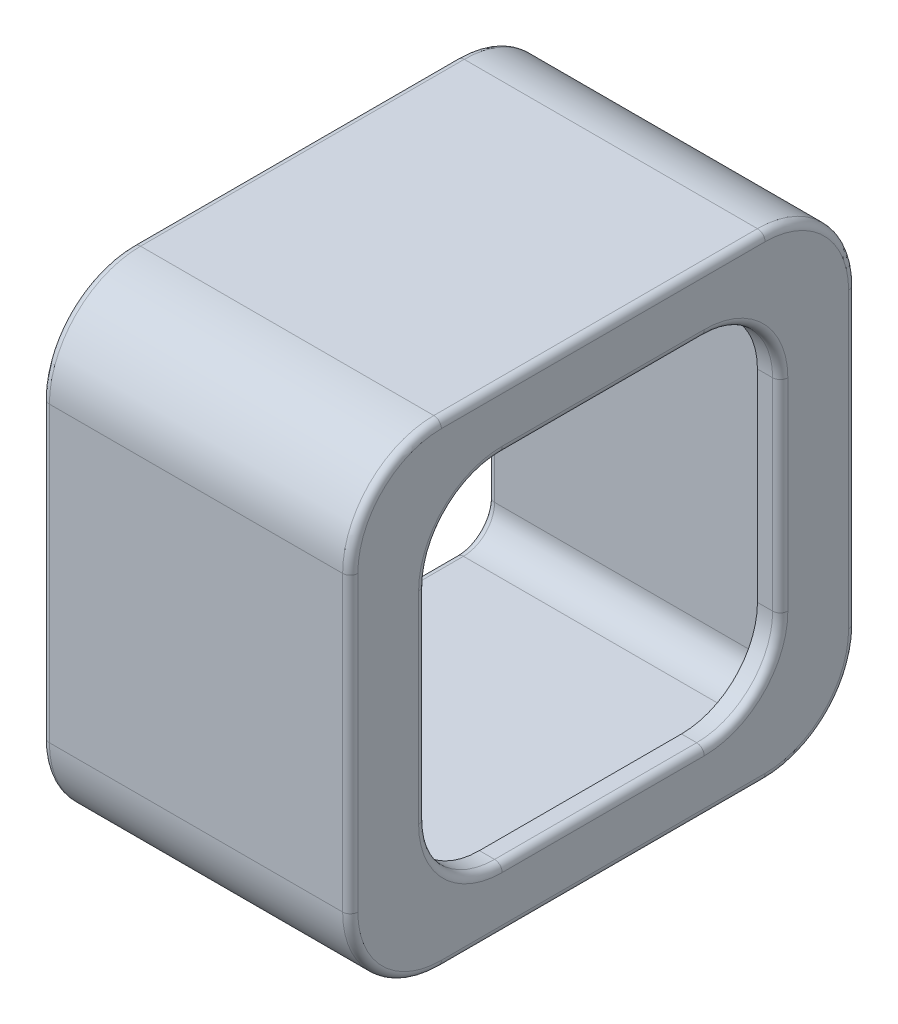
SolidWorks part; units mm, degrees
note: The reader was unsure of these and kept them because the rebuilt part matched: shared geometry of "Sketch1<4>".
ref_plane "Front Plane" through (0, 0, 0) normal (0, 0, 1) x (1, 0, 0)
ref_plane "Top Plane" through (0, 0, 0) normal (0, 1, 0) x (1, 0, 0)
ref_plane "Right Plane" through (0, 0, 0) normal (1, 0, 0) x (0, 0, -1)
ref_plane "Plane1" through (72.6, 0, 0) normal (1, 0, 0) x (0, 0, -1)
sketch "Sketch1" plane through (72.6, 0, 0) normal (1, 0, 0) x (0, 0, -1)
  line L0 (-21.65, 18.55) -> (-8.35, 18.55)
  line L1 (-3.35, 13.55) -> (-3.35, 0.25)
  line L2 (-21.65, -4.75) -> (-8.35, -4.75)
  line L3 (-26.65, 13.55) -> (-26.65, 0.25)
  line L24 (-2.4, 17.5) -> (-2.4, -3.7) construction
  line L25 (-25.6, -5.7) -> (-4.4, -5.7) construction
  line L26 (-27.6, 17.5) -> (-27.6, -3.7) construction
  line L27 (-25.6, 19.5) -> (-4.4, 19.5) construction
  line L28 (-2.4, 17.5) -> (-2.4, -3.7) construction
  line L29 (-25.6, -5.7) -> (-4.4, -5.7) construction
  line L30 (-27.6, 17.5) -> (-27.6, -3.7) construction
  line L31 (-25.6, 19.5) -> (-4.4, 19.5) construction
  line L32 (-25.6, 19.55) -> (-4.4, 19.55)
  line L33 (-2.35, 17.5) -> (-2.35, -3.7)
  line L34 (-25.6, -5.75) -> (-4.4, -5.75)
  line L35 (-27.65, 17.5) -> (-27.65, -3.7)
  line L36 (-25.65, 22.55) -> (-4.35, 22.55)
  line L37 (1.65, 16.55) -> (1.65, -2.75)
  line L38 (-25.65, -8.75) -> (-4.35, -8.75)
  line L39 (-31.65, 16.55) -> (-31.65, -2.75)
  line L40 (-26.65, 17.5) -> (-26.65, -3.7) construction
  line L41 (-25.6, -4.75) -> (-4.4, -4.75) construction
  line L42 (-3.35, 17.5) -> (-3.35, -3.7) construction
  line L43 (-25.6, 18.55) -> (-4.4, 18.55) construction
  arc A24 (-2.4, 17.5) -> (-4.4, 19.5) centre (-4.4, 17.5) ccw construction
  arc A25 (-4.4, -5.7) -> (-2.4, -3.7) centre (-4.4, -3.7) ccw construction
  arc A26 (-27.6, -3.7) -> (-25.6, -5.7) centre (-25.6, -3.7) ccw construction
  arc A27 (-25.6, 19.5) -> (-27.6, 17.5) centre (-25.6, 17.5) ccw construction
  arc A28 (-2.4, 17.5) -> (-4.4, 19.5) centre (-4.4, 17.5) ccw construction
  arc A29 (-4.4, -5.7) -> (-2.4, -3.7) centre (-4.4, -3.7) ccw construction
  arc A30 (-27.6, -3.7) -> (-25.6, -5.7) centre (-25.6, -3.7) ccw construction
  arc A31 (-25.6, 19.5) -> (-27.6, 17.5) centre (-25.6, 17.5) ccw construction
  arc A32 (-2.35, 17.5) -> (-4.4, 19.55) centre (-4.4, 17.5) ccw
  arc A33 (-4.4, -5.75) -> (-2.35, -3.7) centre (-4.4, -3.7) ccw
  arc A34 (-27.65, -3.7) -> (-25.6, -5.75) centre (-25.6, -3.7) ccw
  arc A35 (-25.6, 19.55) -> (-27.65, 17.5) centre (-25.6, 17.5) ccw
  arc A40 (-26.65, 0.25) -> (-21.65, -4.75) centre (-21.65, 0.25) ccw
  arc A41 (-8.35, -4.75) -> (-3.35, 0.25) centre (-8.35, 0.25) ccw
  arc A42 (-3.35, 13.55) -> (-8.35, 18.55) centre (-8.35, 13.55) ccw
  arc A43 (-21.65, 18.55) -> (-26.65, 13.55) centre (-21.65, 13.55) ccw
  arc A44 (-25.6, 18.55) -> (-26.65, 17.5) centre (-25.6, 17.5) ccw construction
  arc A45 (-3.35, 17.5) -> (-4.4, 18.55) centre (-4.4, 17.5) ccw construction
  arc A46 (-4.4, -4.75) -> (-3.35, -3.7) centre (-4.4, -3.7) ccw construction
  arc A47 (-26.65, -3.7) -> (-25.6, -4.75) centre (-25.6, -3.7) ccw construction
  arc A48 (-4.35, -8.75) -> (1.65, -2.75) centre (-4.35, -2.75) ccw
  arc A49 (1.65, 16.55) -> (-4.35, 22.55) centre (-4.35, 16.55) ccw
  arc A50 (-25.65, 22.55) -> (-31.65, 16.55) centre (-25.65, 16.55) ccw
  arc A51 (-31.65, -2.75) -> (-25.65, -8.75) centre (-25.65, -2.75) ccw
  dimension "D6" = 3
  dimension "D4" = 5
  dimension "D8" = 6
  dimension "D2" = 4
  dimension "D3" = 1
  dimension "D5" = 3
  dimension "D7" = 4
  dimension "D1" = 0.05
extrude "Boss-Extrude1" add sketch "Sketch1" against normal offset from surface 0.2 and the other way offset from surface (14.5 mm away) 12
extrude "Boss-Extrude2" add sketch "Sketch1<4>" against normal blind 1.5 from surface at 14.5
sketch "Sketch1<4>" plane through (72.6, 0, 0) normal (1, 0, 0) x (0, 0, -1) same geometry as "Sketch1"
fillet "Fillet1" radius 0.5 32 edges at (66.8, -5.1496, 27.0496) (66.8, 6.9, 27.65) (66.8, 18.9496, 27.0496) (66.8, 19.55, 15) (66.8, 18.9496, 2.9504) (66.8, 6.9, 2.35) (66.8, -5.1496, 2.9504) (66.8, -5.75, 15) (66.8, 22.55, 15) (87.1, 22.55, 15) (66.8, 6.9, 31.65) (87.1, 6.9, 31.65) (66.8, 20.7926, 0.1074) (87.1, 20.7926, 0.1074) (66.8, -8.75, 15) (87.1, -8.75, 15) (66.8, 6.9, -1.65) (87.1, 6.9, -1.65) (87.1, 6.9, 3.35) (87.1, 17.0855, 4.8145) (87.1, 18.55, 15) (87.1, 17.0855, 25.1855) (87.1, 6.9, 26.65) (87.1, -3.2855, 25.1855) (87.1, -4.75, 15) (87.1, -3.2855, 4.8145) (66.8, -6.9926, 29.8926) (66.8, -6.9926, 0.1074) (66.8, 20.7926, 29.8926) (87.1, -6.9926, 0.1074) (87.1, -6.9926, 29.8926) (87.1, 20.7926, 29.8926)
